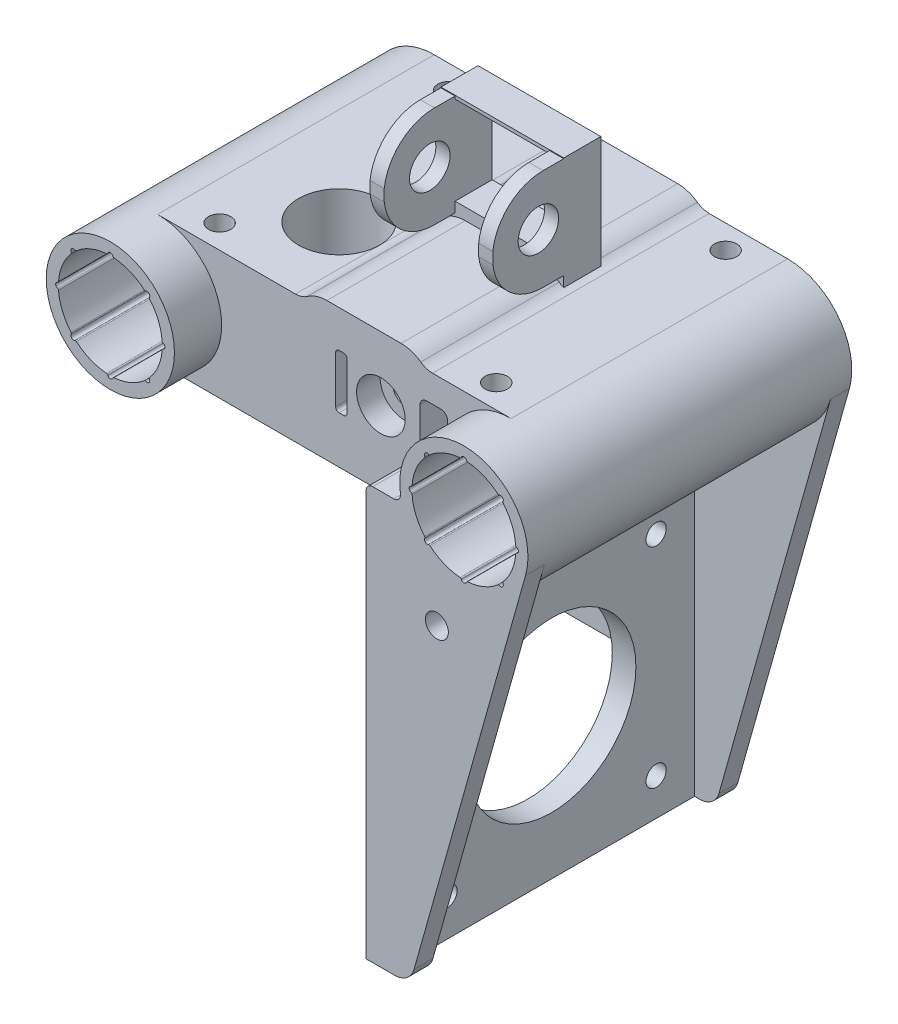
SolidWorks part; units mm, degrees
material "PET"
ref_plane "Front Plane" through (0, 0, 0) normal (0, 0, 1) x (1, 0, 0)
ref_plane "Top Plane" through (0, 0, 0) normal (0, 1, 0) x (1, 0, 0)
ref_plane "Right Plane" through (0, 0, 0) normal (1, 0, 0) x (0, 0, -1)
sketch "Sketch1" plane through (0, 0, 0) normal (0, 0, 1) x (1, 0, 0)
  arc A14 (-5.825, 5.0358) -> (-7.6797, 0.5581) centre (0, 0) ccw
  arc A15 (46.575, 5.0358) -> (44.7203, 0.5581) centre (52.4, 0) ccw
  circle A16 centre (0, 0) radius 9.5
  circle A17 centre (52.4, 0) radius 9.5
  arc A18 (-7.8195, 0.3817) -> (-7.8195, -0.3817) centre (-7.7, 0) ccw
  arc A19 (-5.2593, 5.7991) -> (-5.7991, 5.2593) centre (-5.4447, 5.4447) ccw
  arc A20 (0.3817, 7.8195) -> (-0.3817, 7.8195) centre (0, 7.7) ccw
  arc A21 (5.7991, 5.2593) -> (5.2593, 5.7991) centre (5.4447, 5.4447) ccw
  arc A22 (7.8195, -0.3817) -> (7.8195, 0.3817) centre (7.7, 0) ccw
  arc A23 (-5.7991, -5.2593) -> (-5.2593, -5.7991) centre (-5.4447, -5.4447) ccw
  arc A24 (-0.3817, -7.8195) -> (0.3817, -7.8195) centre (0, -7.7) ccw
  arc A25 (5.2593, -5.7991) -> (5.7991, -5.2593) centre (5.4447, -5.4447) ccw
  arc A26 (44.5805, 0.3817) -> (44.5805, -0.3817) centre (44.7, 0) ccw
  arc A27 (47.1407, 5.7991) -> (46.6009, 5.2593) centre (46.9553, 5.4447) ccw
  arc A28 (52.7817, 7.8195) -> (52.0183, 7.8195) centre (52.4, 7.7) ccw
  arc A29 (58.1991, 5.2593) -> (57.6593, 5.7991) centre (57.8447, 5.4447) ccw
  arc A30 (60.2195, -0.3817) -> (60.2195, 0.3817) centre (60.1, 0) ccw
  arc A31 (46.6009, -5.2593) -> (47.1407, -5.7991) centre (46.9553, -5.4447) ccw
  arc A32 (52.0183, -7.8195) -> (52.7817, -7.8195) centre (52.4, -7.7) ccw
  arc A33 (57.6593, -5.7991) -> (58.1991, -5.2593) centre (57.8447, -5.4447) ccw
  arc A34 (51.8419, 7.6797) -> (47.3642, 5.825) centre (52.4, 0) ccw
  arc A35 (44.7203, -0.5581) -> (46.575, -5.0358) centre (52.4, 0) ccw
  arc A36 (57.4358, 5.825) -> (52.9581, 7.6797) centre (52.4, 0) ccw
  arc A37 (60.0797, 0.5581) -> (58.225, 5.0358) centre (52.4, 0) ccw
  arc A38 (58.225, -5.0358) -> (60.0797, -0.5581) centre (52.4, 0) ccw
  arc A39 (52.9581, -7.6797) -> (57.4358, -5.825) centre (52.4, 0) ccw
  arc A40 (47.3642, -5.825) -> (51.8419, -7.6797) centre (52.4, 0) ccw
  arc A41 (-7.6797, -0.5581) -> (-5.825, -5.0358) centre (0, 0) ccw
  arc A42 (-5.0358, -5.825) -> (-0.5581, -7.6797) centre (0, 0) ccw
  arc A43 (0.5581, -7.6797) -> (5.0358, -5.825) centre (0, 0) ccw
  arc A44 (5.825, -5.0358) -> (7.6797, -0.5581) centre (0, 0) ccw
  arc A45 (7.6797, 0.5581) -> (5.825, 5.0358) centre (0, 0) ccw
  arc A46 (5.0358, 5.825) -> (0.5581, 7.6797) centre (0, 0) ccw
  arc A47 (-0.5581, 7.6797) -> (-5.0358, 5.825) centre (0, 0) ccw
  arc A48 (58.1991, -5.2593) -> (58.225, -5.0358) centre (58.3763, -5.1666) cw
  arc A49 (57.6593, -5.7991) -> (57.4358, -5.825) centre (57.5666, -5.9763) ccw
  arc A50 (52.0183, -7.8195) -> (51.8419, -7.6797) centre (51.8274, -7.8792) ccw
  arc A51 (47.1407, -5.7991) -> (47.3642, -5.825) centre (47.2334, -5.9763) cw
  arc A52 (46.6009, -5.2593) -> (46.575, -5.0358) centre (46.4237, -5.1666) ccw
  arc A53 (60.2195, -0.3817) -> (60.0797, -0.5581) centre (60.2792, -0.5726) ccw
  arc A54 (60.2195, 0.3817) -> (60.0797, 0.5581) centre (60.2792, 0.5726) cw
  arc A55 (58.1991, 5.2593) -> (58.225, 5.0358) centre (58.3763, 5.1666) ccw
  arc A56 (57.6593, 5.7991) -> (57.4358, 5.825) centre (57.5666, 5.9763) cw
  arc A57 (44.5805, -0.3817) -> (44.7203, -0.5581) centre (44.5208, -0.5726) cw
  arc A58 (44.5805, 0.3817) -> (44.7203, 0.5581) centre (44.5208, 0.5726) ccw
  arc A59 (46.6009, 5.2593) -> (46.575, 5.0358) centre (46.4237, 5.1666) cw
  arc A60 (47.1407, 5.7991) -> (47.3642, 5.825) centre (47.2334, 5.9763) ccw
  arc A61 (52.0183, 7.8195) -> (51.8419, 7.6797) centre (51.8274, 7.8792) cw
  arc A62 (52.7817, 7.8195) -> (52.9581, 7.6797) centre (52.9726, 7.8792) ccw
  arc A63 (7.8195, -0.3817) -> (7.6797, -0.5581) centre (7.8792, -0.5726) ccw
  arc A64 (7.8195, 0.3817) -> (7.6797, 0.5581) centre (7.8792, 0.5726) cw
  arc A65 (5.7991, -5.2593) -> (5.825, -5.0358) centre (5.9763, -5.1666) cw
  arc A66 (5.2593, -5.7991) -> (5.0358, -5.825) centre (5.1666, -5.9763) ccw
  arc A67 (-0.3817, -7.8195) -> (-0.5581, -7.6797) centre (-0.5726, -7.8792) ccw
  arc A68 (-5.2593, -5.7991) -> (-5.0358, -5.825) centre (-5.1666, -5.9763) cw
  arc A69 (-5.7991, -5.2593) -> (-5.825, -5.0358) centre (-5.9763, -5.1666) ccw
  arc A70 (-7.8195, -0.3817) -> (-7.6797, -0.5581) centre (-7.8792, -0.5726) cw
  arc A71 (-7.8195, 0.3817) -> (-7.6797, 0.5581) centre (-7.8792, 0.5726) ccw
  arc A72 (5.7991, 5.2593) -> (5.825, 5.0358) centre (5.9763, 5.1666) ccw
  arc A73 (5.2593, 5.7991) -> (5.0358, 5.825) centre (5.1666, 5.9763) cw
  arc A74 (-5.7991, 5.2593) -> (-5.825, 5.0358) centre (-5.9763, 5.1666) cw
  arc A75 (-5.2593, 5.7991) -> (-5.0358, 5.825) centre (-5.1666, 5.9763) ccw
  arc A76 (-0.3817, 7.8195) -> (-0.5581, 7.6797) centre (-0.5726, 7.8792) cw
  arc A77 (0.3817, 7.8195) -> (0.5581, 7.6797) centre (0.5726, 7.8792) ccw
  arc A78 (0.3817, -7.8195) -> (0.5581, -7.6797) centre (0.5726, -7.8792) cw
  arc A79 (52.7817, -7.8195) -> (52.9581, -7.6797) centre (52.9726, -7.8792) cw
extrude "Boss-Extrude1" add sketch "Sketch1" along normal blind 48
sketch "Sketch29" plane through (0, 0, 0) normal (0, 0, -1) x (-1, 0, 0)
  line L6 (-52.4, 9.5) -> (-40.7637, 9.5)
  line L45 (9.5, -36.55) -> (9.5, 0)
  line L66 (-45.0149, -61.4114) -> (-61.5459, -2.5695)
  line L74 (-3.3, -49.35) -> (-31.9, -49.35)
  line L76 (-38.9, 4.5) -> (-38.9, -1.5)
  line L77 (-34.9, -52.35) -> (-34.9, -60.6)
  line L78 (-37.9, -63.6) -> (-42.1267, -63.6)
  line L80 (-43, -1.5) -> (-43, -1.3748)
  line L81 (-43, 1.3748) -> (-43, 4.5)
  line L82 (-39.9, 5.5) -> (-42, 5.5)
  line L83 (-20.4363, 9.5) -> (0, 9.5)
  line L84 (-39.9, -2.5) -> (-42, -2.5)
  line L101 (-36.1, 11) -> (-25.1, 11)
  circle A58 centre (-3.3, -36.55) radius 1.5
  circle A59 centre (-17.3, -36.55) radius 1.5
  arc A65 (0, 9.5) -> (9.5, 0) centre (0, 0) ccw
  arc A73 (-42.1267, -63.6) -> (-45.0149, -61.4114) centre (-42.1267, -60.6) cw
  arc A75 (9.5, -36.55) -> (-3.3, -49.35) centre (-3.3, -36.55) cw
  arc A87 (-31.9, -49.35) -> (-34.9, -52.35) centre (-31.9, -52.35) ccw
  arc A88 (-34.9, -60.6) -> (-37.9, -63.6) centre (-37.9, -60.6) cw
  arc A89 (-38.9, -1.5) -> (-39.9, -2.5) centre (-39.9, -1.5) cw
  arc A90 (-39.9, 5.5) -> (-38.9, 4.5) centre (-39.9, 4.5) cw
  arc A93 (-43, 4.5) -> (-42, 5.5) centre (-42, 4.5) cw
  arc A102 (-61.5459, -2.5695) -> (-43, -1.3748) centre (-52.4, 0) ccw
  arc A103 (-43, -1.5) -> (-42, -2.5) centre (-42, -1.5) ccw
  arc A104 (-43, 1.3748) -> (-52.4, 9.5) centre (-52.4, 0) ccw
  arc A127 (-36.1, 11) -> (-39.0148, 10.0625) centre (-36.1, 6) ccw
  arc A128 (-22.1852, 10.0625) -> (-25.1, 11) centre (-25.1, 6) ccw
  arc A129 (-22.1852, 10.0625) -> (-20.4363, 9.5) centre (-20.4363, 12.5) ccw
  arc A130 (-39.0148, 10.0625) -> (-40.7637, 9.5) centre (-40.7637, 12.5) cw
extrude "Boss-Extrude18" add sketch "Sketch29" against normal blind 3
sketch "Sketch36" plane through (0, 0, 3) normal (0, 0, 1) x (1, 0, 0)
  line L9 (38.9, 4.5) -> (38.9, -1.5)
  line L15 (39.9, -2.5) -> (42, -2.5)
  line L17 (43, -1.5) -> (43, -1.3748)
  line L19 (43, 1.3748) -> (43, 4.5)
  line L21 (42, 5.5) -> (39.9, 5.5)
  line L37 (0, -9.5) -> (52.4, -9.5)
  line L38 (0, 9.5) -> (20.4363, 9.5)
  line L40 (40.7637, 9.5) -> (52.4, 9.5)
  line L57 (36.1, 11) -> (25.1, 11)
  line L58 (26.4, 5) -> (26.4, -2)
  line L59 (27.6, -2.5) -> (26.9, -2.5)
  line L60 (28.1, 5) -> (28.1, -2)
  line L61 (27.6, 5.5) -> (26.9, 5.5)
  arc A19 (39.9, 5.5) -> (38.9, 4.5) centre (39.9, 4.5) ccw
  arc A25 (38.9, -1.5) -> (39.9, -2.5) centre (39.9, -1.5) ccw
  arc A26 (42, -2.5) -> (43, -1.5) centre (42, -1.5) ccw
  arc A27 (43, 4.5) -> (42, 5.5) centre (42, 4.5) ccw
  arc A67 (0, -9.5) -> (0, 9.5) centre (0, 0) ccw
  arc A68 (52.4, 9.5) -> (43, 1.3748) centre (52.4, 0) ccw
  arc A69 (43, -1.3748) -> (52.4, -9.5) centre (52.4, 0) ccw
  arc A81 (39.0148, 10.0625) -> (40.7637, 9.5) centre (40.7637, 12.5) ccw
  arc A82 (22.1852, 10.0625) -> (20.4363, 9.5) centre (20.4363, 12.5) cw
  arc A83 (22.1852, 10.0625) -> (25.1, 11) centre (25.1, 6) cw
  arc A84 (36.1, 11) -> (39.0148, 10.0625) centre (36.1, 6) cw
  circle A85 centre (33.1, 1.5) radius 1.7
  arc A86 (27.6, 5.5) -> (28.1, 5) centre (27.6, 5) cw
  arc A87 (26.9, 5.5) -> (26.4, 5) centre (26.9, 5) ccw
  arc A88 (28.1, -2) -> (27.6, -2.5) centre (27.6, -2) cw
  arc A89 (26.9, -2.5) -> (26.4, -2) centre (26.9, -2) cw
  point P1 (20.1449, 9.5)
  point P2 (0, 0)
extrude "Boss-Extrude26" add sketch "Sketch36" along normal blind 38
sketch "Sketch14" plane through (0, -9.5, 0) normal (0, -1, 0) x (1, 0, 0)
  circle A2 centre (14.4, 28.5) radius 4.125
extrude "Boss-Extrude27" add sketch "Sketch14" along normal blind 4
sketch "Sketch34" plane through (0, 9.5, 0) normal (0, 1, 0) x (1, 0, 0)
  circle A4 centre (14.4, -28.5) radius 6
extrude "Cut-Extrude17" cut sketch "Sketch34" against normal blind 10
sketch "Sketch38" plane through (0, -0.5, 0) normal (0, 1, 0) x (1, 0, 0)
  circle A2 centre (14.5, -28.5) radius 2.15
extrude "Cut-Extrude18" cut sketch "Sketch38" against normal up to surface (13 mm away) up to face at (18.525, -13.5, 28.5)
sketch "Sketch39" plane through (0, 0, 3) normal (0, 0, 1) x (1, 0, 0)
  line L12 (41.4, -63.6) -> (37.9, -63.6)
  line L13 (37.9, -3.5) -> (37.9, -63.6)
  line L15 (38.9, -2.5) -> (42, -2.5)
  line L17 (41.4, -63.6) -> (41.4, -9.5)
  line L20 (41.4, -9.5) -> (52.4, -9.5)
  line L21 (43, -1.5) -> (43, -1.3748)
  arc A2 (37.9, -3.5) -> (38.9, -2.5) centre (38.9, -3.5) cw
  arc A4 (42, -2.5) -> (43, -1.5) centre (42, -1.5) ccw
  arc A6 (43, -1.3748) -> (52.4, -9.5) centre (52.4, 0) ccw
extrude "Boss-Extrude43" add sketch "Sketch39" along normal offset from surface (42.2 mm away) 2.8 up to face at (61.9, 0, 48)
sketch "Sketch7" plane through (0, 0, 45.2) normal (0, 0, 1) x (1, 0, 0)
  line L14 (37.9, -63.6) -> (42.1267, -63.6)
  line L18 (43, -1.3748) -> (43, -1.5)
  line L19 (45.0149, -61.4114) -> (61.5459, -2.5695)
  line L21 (37.9, -3.5) -> (37.9, -63.6)
  line L26 (38.9, -2.5) -> (42, -2.5)
  circle A4 centre (48.4, -15.6) radius 1.7
  arc A6 (42.1267, -63.6) -> (45.0149, -61.4114) centre (42.1267, -60.6) ccw
  arc A22 (38.9, -2.5) -> (37.9, -3.5) centre (38.9, -3.5) ccw
  arc A30 (42, -2.5) -> (43, -1.5) centre (42, -1.5) ccw
  arc A31 (43, -1.3748) -> (61.5459, -2.5695) centre (52.4, 0) ccw
extrude "Boss-Extrude44" add sketch "Sketch7" along normal up to surface (2.8 mm away) up to face at (61.9, 0, 48)
sketch "Sketch69" plane through (37.9, 0, 0) normal (-1, 0, 0) x (0, 0, 1)
  line L0 (3, -9.5) -> (3, -25)
  line L2 (3, -25) -> (18.5, -9.5)
  line L4 (18.5, -9.5) -> (3, -9.5)
extrude "Boss-Extrude42" add sketch "Sketch69" along normal blind 6.5 from offset 25
sketch "Sketch40" plane through (0, 0, 45.2) normal (0, 0, -1) x (-1, 0, 0)
  line L23 (-42.2, -12.85) -> (-41.4, -12.85)
  line L24 (-42.2, -18.15) -> (-41.4, -18.15)
  line L26 (-41.4, -12.85) -> (-41.4, -18.15)
  line L28 (-42.7, -13.35) -> (-42.7, -17.65)
  arc A10 (-42.2, -12.85) -> (-42.7, -13.35) centre (-42.2, -13.35) ccw
  arc A11 (-42.7, -17.65) -> (-42.2, -18.15) centre (-42.2, -17.65) ccw
extrude "Boss-Extrude45" add sketch "Sketch40" along normal blind 10
sketch "Sketch47" plane through (41.4, 0, 0) normal (1, 0, 0) x (0, 0, -1)
  circle A0 centre (-8.5, -15.55) radius 1.5
  circle A1 centre (-8.5, -15.55) radius 4
extrude "Boss-Extrude40" add sketch "Sketch47" along normal blind 1.4
sketch "Sketch20" plane through (41.4, 0, 0) normal (1, 0, 0) x (0, 0, -1)
  circle A0 centre (-8.5, -58.1) radius 1.5
  circle A1 centre (-39.5, -58.1) radius 1.5
  circle A2 centre (-8.5, -27.1) radius 1.5
  circle A3 centre (-24, -42.6) radius 12.5
  circle A5 centre (-8.5, -15.55) radius 1.5
extrude "Cut-Extrude19" cut sketch "Sketch20" against normal up to surface (3.5 mm away) up to face at (37.9, -25.5333, 30.6667)
sketch "Sketch43" plane through (0, 0, 41) normal (0, 0, 1) x (1, 0, 0)
  circle A1 centre (33.1, 1.5) radius 3.6
extrude "Cut-Extrude22" cut sketch "Sketch43" against normal blind 3.5
sketch "Sketch62" plane through (0, 0, 3) normal (0, 0, 1) x (1, 0, 0)
  line L4 (61.9, -54.1) -> (61.9, 0)
  line L5 (52.4, -63.6) -> (41.4, -63.6)
  line L6 (41.4, -63.6) -> (41.4, -9.5)
  line L7 (41.4, -9.5) -> (52.4, -9.5)
  arc A1 (52.4, -9.5) -> (61.9, 0) centre (52.4, 0) ccw
  arc A2 (52.4, -63.6) -> (61.9, -54.1) centre (52.4, -54.1) ccw
extrude "Cut-Extrude30" cut sketch "Sketch62" against normal blind 0.2
sketch "Sketch70" plane through (0, 0, 0) normal (0, 0, -1) x (-1, 0, 0)
  line L6 (-36.1, -5) -> (-25.1, -5)
  line L7 (-23.1, -3) -> (-23.1, 6)
  line L8 (-25.1, 8) -> (-36.1, 8)
  line L9 (-38.1, 6) -> (-38.1, -3)
  arc A1 (-38.1, 6) -> (-36.1, 8) centre (-36.1, 6) cw
  arc A3 (-25.1, 8) -> (-23.1, 6) centre (-25.1, 6) cw
  arc A5 (-23.1, -3) -> (-25.1, -5) centre (-25.1, -3) cw
  arc A6 (-36.1, -5) -> (-38.1, -3) centre (-36.1, -3) cw
extrude "Cut-Extrude33" cut sketch "Sketch70" against normal blind 25
sketch "Sketch66" plane through (0, 0, 25) normal (0, 0, -1) x (-1, 0, 0)
  line L1 (-26.9, 5.5) -> (-28.4, 5.5)
  line L2 (-26.4, 5) -> (-26.4, -2)
  line L3 (-26.9, -2.5) -> (-28.4, -2.5)
  line L4 (-28.9, 5) -> (-28.9, -2)
  arc A0 (-26.4, -2) -> (-26.9, -2.5) centre (-26.9, -2) cw
  arc A1 (-28.4, -2.5) -> (-28.9, -2) centre (-28.4, -2) cw
  arc A2 (-28.4, 5.5) -> (-28.9, 5) centre (-28.4, 5) ccw
  arc A3 (-26.9, 5.5) -> (-26.4, 5) centre (-26.9, 5) cw
extrude "Cut-Extrude32" cut sketch "Sketch66" against normal blind 8
sketch "Sketch72" plane through (0, 9.5, 0) normal (0, 1, 0) x (1, 0, 0)
  circle A0 centre (46.7, -37.5) radius 1.65
  circle A1 centre (46.7, -3.5) radius 1.65
  circle A2 centre (5.7, -3.5) radius 1.65
  circle A3 centre (5.7, -37.5) radius 1.65
extrude "Cut-Extrude34" cut sketch "Sketch72" against normal up to next
sketch "Sketch74" plane through (0, 9.5, 0) normal (0, 1, 0) x (1, 0, 0)
  line L1 (21.5, -31) -> (39.7, -31)
  line L2 (21.5, -31) -> (21.5, -15)
  line L3 (21.5, -15) -> (39.7, -15)
  line L4 (39.7, -31) -> (39.7, -15)
extrude "Boss-Extrude46" add sketch "Sketch74" along normal blind 16.85
sketch "Sketch75" plane through (0, 0, 31) normal (0, 0, 1) x (1, 0, 0)
  line L1 (23.6, 24.25) -> (37.6, 24.25)
  line L2 (23.6, 24.25) -> (23.6, 12.75)
  line L3 (23.6, 12.75) -> (37.6, 12.75)
  line L4 (37.6, 24.25) -> (37.6, 12.75)
extrude "Cut-Extrude35" cut sketch "Sketch75" against normal up to surface (16 mm away) up to face at (30.6, 14.3284, 15)
sketch "Sketch76" plane through (39.7, 0, 0) normal (1, 0, 0) x (0, 0, -1)
  line L0 (-23.55, 26.25) -> (-31, 26.25)
  line L1 (-23.55, 11.25) -> (-31, 11.25)
  line L3 (-31, 11.25) -> (-31, 17.8854)
  line L4 (-31, 19.6146) -> (-31, 26.25)
  arc A0 (-23.55, 26.25) -> (-31, 19.6146) centre (-23.55, 18.75) ccw
  circle A2 centre (-24.25, 19) radius 3
  arc A3 (-31, 17.8854) -> (-23.55, 11.25) centre (-23.55, 18.75) ccw
extrude "Cut-Extrude36" cut sketch "Sketch76" against normal up to surface (18.2 mm away) up to face at (21.5, 18.0225, 23)
sketch "Sketch77" plane through (0, 0, 31) normal (0, 0, 1) x (1, 0, 0)
  line L3 (23.6, 11.25) -> (23.6, 26.25)
  line L6 (37.6, 26.25) -> (37.6, 11.25)
  line L12 (25.1, 11) -> (36.1, 11)
  line L13 (23.6, 11.25) -> (21.5, 11.25)
  line L14 (37.6, 11.25) -> (39.7, 11.25)
  line L15 (39.7, 11.25) -> (39.7, 9.6949)
  line L16 (21.5, 11.25) -> (21.5, 9.6949)
  line L17 (37.6, 26.25) -> (39.7, 26.25)
  line L18 (21.5, 26.35) -> (39.7, 26.35)
  line L19 (21.5, 26.35) -> (21.5, 26.25)
  line L20 (21.5, 26.25) -> (23.6, 26.25)
  line L21 (39.7, 26.35) -> (39.7, 26.25)
  arc A0 (25.1, 11) -> (22.1852, 10.0625) centre (25.1, 6) ccw
  arc A1 (39.0148, 10.0625) -> (36.1, 11) centre (36.1, 6) ccw
  arc A5 (21.5, 9.6949) -> (22.1852, 10.0625) centre (20.4363, 12.5) ccw
  arc A6 (39.0148, 10.0625) -> (39.7, 9.6949) centre (40.7637, 12.5) ccw
extrude "Cut-Extrude37" cut sketch "Sketch77" against normal blind 10.5
chamfer "Chamfer1" distance 1.6 angle 45 1 edges at (30.6, 24.25, 20.5)
